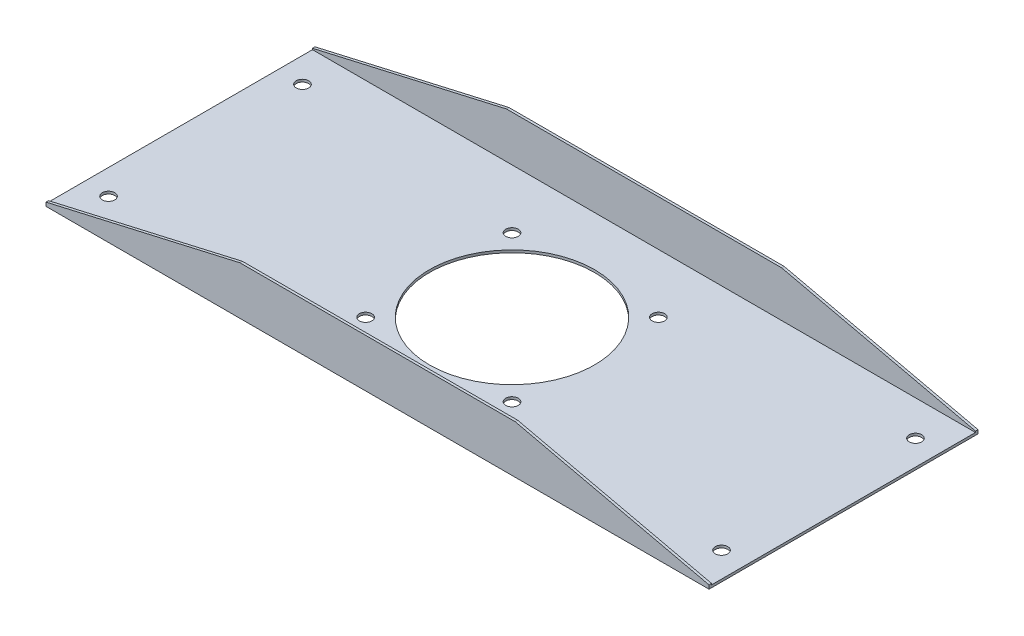
SolidWorks part; units mm, degrees
ref_plane "Спереди" through (0, 0, 0) normal (0, 0, 1) x (1, 0, 0)
ref_plane "Сверху" through (0, 0, 0) normal (0, 1, 0) x (1, 0, 0)
ref_plane "Справа" through (0, 0, 0) normal (1, 0, 0) x (0, 0, -1)
sketch "Эскиз1" plane through (0, 0, 0) normal (1, 0, 0) x (0, 0, -1)
  line L0 (-105, 0) -> (110, 0)
  line L1 (110, 0) -> (110, 38.5)
  line L2 (-105, 0) -> (-105, 38.5)
  dimension "D1" = 215
  dimension "D2" = 38.5
  dimension "D3" = 38.5
extrude "Вытянуть-Тонкостенный1" add sketch "Эскиз1" along normal blind 530 thin thin type one direction wall 2
sketch "Эскиз2" plane through (0, 0, -110) normal (0, 0, -1) x (-1, 0, 0)
  line L0 (-530, 0) -> (-530, 3)
  line L1 (-530, 38.5) -> (-530, 0) construction
  line L2 (-530, 3) -> (-375, 38.5)
  line L3 (-530, 38.5) -> (0, 38.5) construction
  line L4 (-375, 38.5) -> (-155, 38.5)
  line L5 (-155, 38.5) -> (0, 3)
  line L6 (0, 38.5) -> (0, 0) construction
  line L7 (0, 3) -> (0, 0)
  line L8 (0, 0) -> (-530, 0)
  dimension "D1" = 155
  dimension "D2" = 155
  dimension "D3" = 3
extrude "Вырез-Вытянуть2" cut sketch "Эскиз2" against normal through all flip side to cut
sketch "Эскиз3" plane through (0, 2, 0) normal (0, 1, 0) x (1, 0, 0)
  line L0 (20, 115.302) -> (20, -116.3672) construction
  line L1 (0, 108) -> (0, -103) construction
  line L2 (0, 110) -> (155, 110) construction
  line L3 (510, 126.018) -> (510, -161.4271) construction
  line L4 (530, 108) -> (530, -103) construction
  line L5 (0, 108) -> (530, -103) construction
  line L6 (530, 108) -> (0, -103) construction
  line L7 (193.3427, 74.1573) -> (265, 2.5) construction
  line L8 (265, 2.5) -> (336.6573, -69.1573) construction
  line L9 (336.6573, 74.1573) -> (193.3427, -69.1573) construction
  line L10 (0, -105) -> (155, -105) construction
  line L11 (-19.3922, 80) -> (530, 80) construction
  line L12 (-19.3922, -75) -> (541.7561, -75) construction
  circle A0 centre (20, 80) radius 5
  circle A1 centre (20, -75) radius 5
  circle A2 centre (510, 80) radius 5
  circle A3 centre (510, -75) radius 5
  circle A4 centre (265, 2.5) radius 66
  circle A5 centre (323.514, 61.014) radius 5
  circle A6 centre (323.514, -56.014) radius 5
  circle A7 centre (206.486, -56.014) radius 5
  circle A8 centre (206.486, 61.014) radius 5
  point P43 (265, 2.5)
  dimension "D2" = 30
  dimension "D5" = 4
  dimension "D1" = 20
  dimension "D3" = 30
  dimension "D4" = 20
extrude "Вырез-Вытянуть3" cut sketch "Эскиз3" against normal through all
